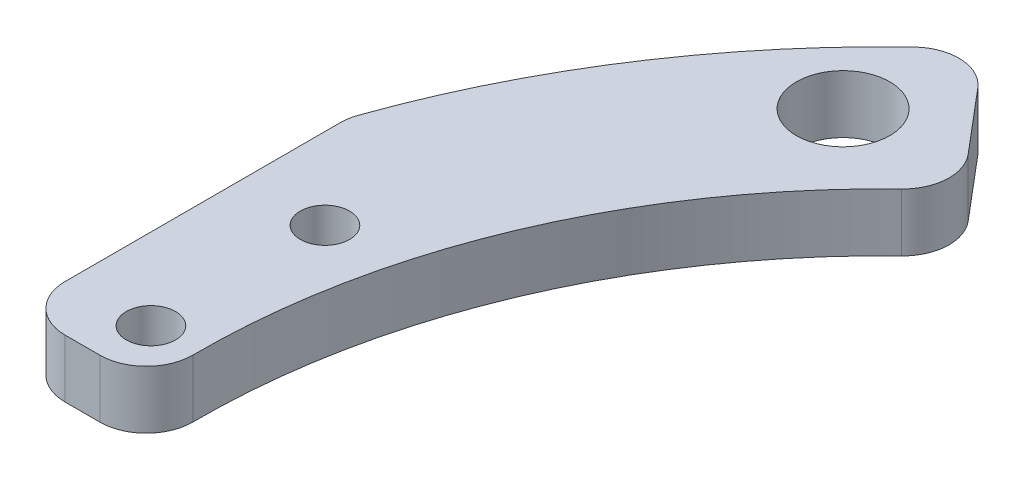
SolidWorks part; units mm, degrees
ref_plane "Front Plane" through (0, 0, 0) normal (0, 0, 1) x (1, 0, 0)
ref_plane "Top Plane" through (0, 0, 0) normal (0, 1, 0) x (1, 0, 0)
ref_plane "Right Plane" through (0, 0, 0) normal (1, 0, 0) x (0, 0, -1)
sketch "Sketch1" plane through (0, 0, 0) normal (0, 1, 0) x (1, 0, 0)
  line L0 (0, 0) -> (-63, 0) construction
  line L1 (-47.7573, 56.5264) -> (-38.0768, 45.0684)
  line L2 (0, 0) -> (-49.3664, 46.0349) construction
  line L15 (-63, -30) -> (-63, 30) construction
  line L16 (-55.5, 0) -> (-70.5, 0) construction
  line L17 (-70.4495, -22.6467) -> (-56.1692, -18.0562)
  circle A0 centre (0, 0) radius 55 construction
  circle A1 centre (0, 0) radius 62.5 construction
  circle A2 centre (-49.3664, 46.0349) radius 3.75 construction
  circle A5 centre (-49.3664, 46.0349) radius 4.025
  circle A7 centre (-63, 0) radius 2.125
  circle A8 centre (-63, -15) radius 2.125
  circle A9 centre (-63, 15) radius 2.125
  arc A10 (-38.0768, 45.0684) -> (-56.1692, -18.0562) centre (0, 0) ccw
  arc A11 (-47.7573, 56.5264) -> (-70.4495, -22.6467) centre (0, 0) ccw
  point P7 (-63, 0)
  dimension "D1" = 110
  dimension "D4" = 125
  dimension "D5" = 7.5
  dimension "D11" = 15
  dimension "D12" = 15
  dimension "D13" = 8.05
  dimension "D8" = 4.25
  dimension "D10" = 5
  dimension "D2" = 59
  dimension "D9" = 15
  dimension "D14" = 8
  dimension "D3" = 63
  dimension "D6" = 67.5
  dimension "D7" = 43
extrude "Boss-Extrude1" add sketch "Sketch1" along normal blind 5
sketch "Sketch2" plane through (0, 5, 0) normal (0, 1, 0) x (1, 0, 0)
  line L0 (0, 0) -> (-84.4523, 0) construction
  line L2 (-70, 27.6661) -> (-98.9046, 27.6661)
  line L3 (-70, 27.6661) -> (-70, -27.6661)
  line L4 (-70, -27.6661) -> (-98.9046, -27.6661)
  line L5 (-98.9046, 27.6661) -> (-98.9046, -27.6661)
  line L6 (-84.4523, -27.6661) -> (-84.4523, 27.6661) construction
  line L7 (-70, 0) -> (-98.9046, 0) construction
  dimension "D1" = 70
extrude "Cut-Extrude1" cut sketch "Sketch2" against normal through all both and the other way through all
sketch "Sketch3" plane through (0, 5, 0) normal (0, 1, 0) x (1, 0, 0)
  line L0 (-70, -22.5022) -> (-70, 24) construction
  line L1 (-70, -4.3988) -> (-45.7929, -4.3988)
  line L2 (-70, -4.3988) -> (-70, -25.4993)
  line L3 (-70, -25.4993) -> (-45.7929, -25.4993)
  line L4 (-45.7929, -4.3988) -> (-45.7929, -25.4993)
  line L5 (-57.8964, -25.4993) -> (-57.8964, -4.3988) construction
  line L6 (-70, -14.949) -> (-45.7929, -14.949) construction
  point P56 (-57.8964, -14.949)
extrude "Cut-Extrude2" cut sketch "Sketch3" against normal through all both and the other way through all
fillet "Fillet1" radius 4 5 edges at (-70, 2.5, -24) (-70, 2.5, 4.3988) (-58.8358, 2.5, 4.3988) (-38.0768, 2.5, -45.0684) (-47.7573, 2.5, -56.5264)
